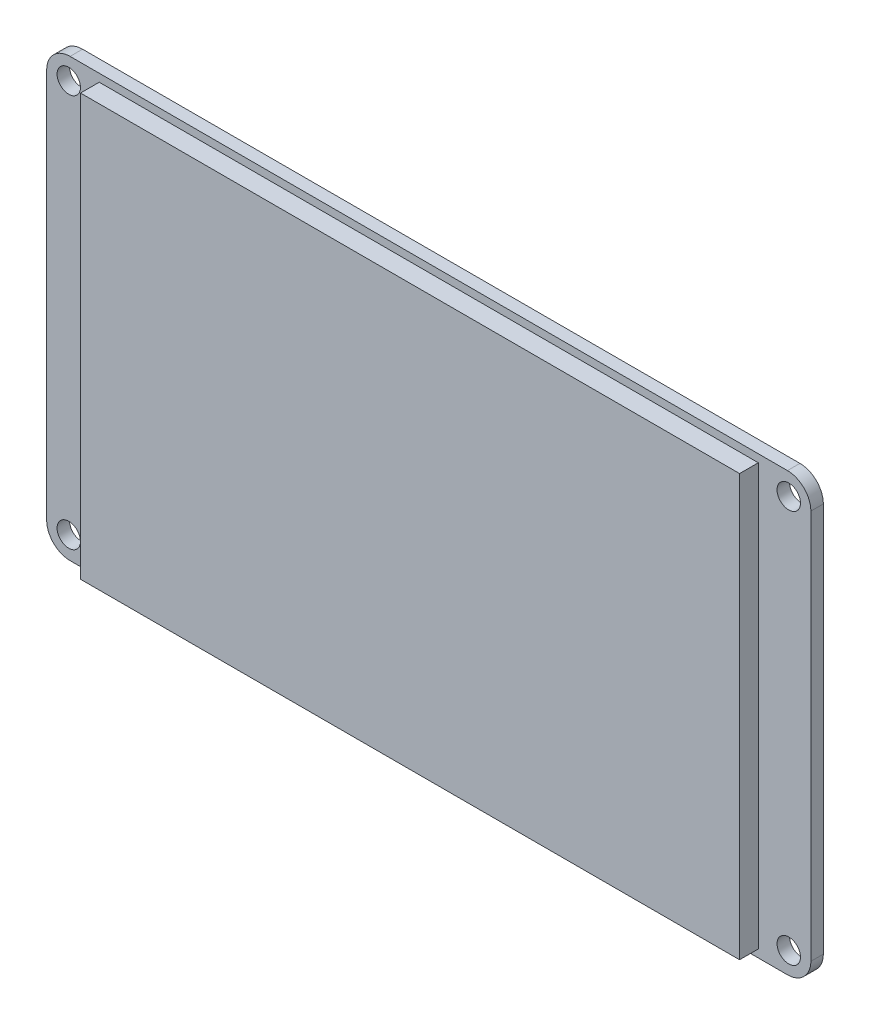
SolidWorks part; units mm, degrees
ref_plane "Plano frontal" through (0, 0, 0) normal (0, 0, 1) x (1, 0, 0)
ref_plane "Plano superior" through (0, 0, 0) normal (0, 1, 0) x (1, 0, 0)
ref_plane "Plano direito" through (0, 0, 0) normal (1, 0, 0) x (0, 0, -1)
sketch "Esboço1" plane through (0, 0, 0) normal (0, 0, 1) x (1, 0, 0)
  line L0 (0, 11.5762) -> (0, 0) construction
  line L1 (-46, 28) -> (46, 28)
  line L2 (-49, 25) -> (-49, -25)
  line L3 (-46, -28) -> (46, -28)
  line L4 (49, 25) -> (49, -25)
  line L5 (-49, 28) -> (49, -28) construction
  line L6 (-49, -28) -> (49, 28) construction
  line L7 (0, 0) -> (13.002, 0) construction
  line L9 (-42.26, 27) -> (42.26, 27)
  line L10 (-42.26, 27) -> (-42.26, -27)
  line L11 (-42.26, -27) -> (42.26, -27)
  line L12 (42.26, 27) -> (42.26, -27)
  line L13 (-42.26, 27) -> (42.26, -27) construction
  line L14 (-42.26, -27) -> (42.26, 27) construction
  circle A0 centre (-46.165, 25.21) radius 1.5
  circle A1 centre (46.165, 25.21) radius 1.5
  circle A2 centre (-46.165, -25.21) radius 1.5
  circle A3 centre (46.165, -25.21) radius 1.5
  arc A4 (46, 28) -> (49, 25) centre (46, 25) cw
  arc A5 (46, -28) -> (49, -25) centre (46, -25) ccw
  arc A6 (-49, -25) -> (-46, -28) centre (-46, -25) ccw
  arc A7 (-46, 28) -> (-49, 25) centre (-46, 25) ccw
  point P0 (0, 0)
  dimension "D1" = 3
  dimension "D8" = 3
  dimension "D2" = 56
  dimension "D3" = 98
  dimension "D4" = 92.33
  dimension "D5" = 50.42
  dimension "D6" = 84.52
  dimension "D7" = 1
extrude "Ressalto-extrusão1" add sketch "Esboço1" along normal blind 1.6 contours L4 L1 L2 L3 A3 A1 A0 L9 L12 L11 L10 A2 | L12 L9 L10 L11 region at (0, 27.8871, 0) region at (0, 0, 0)
extrude "Ressalto-extrusão2" add sketch "Esboço1<3>" along normal blind 4 contours L12 L9 L10 L11 region at (0, 0, 0)
sketch "Esboço1<3>" plane through (0, 0, 0) normal (0, 0, 1) x (1, 0, 0) same geometry as "Esboço1"
